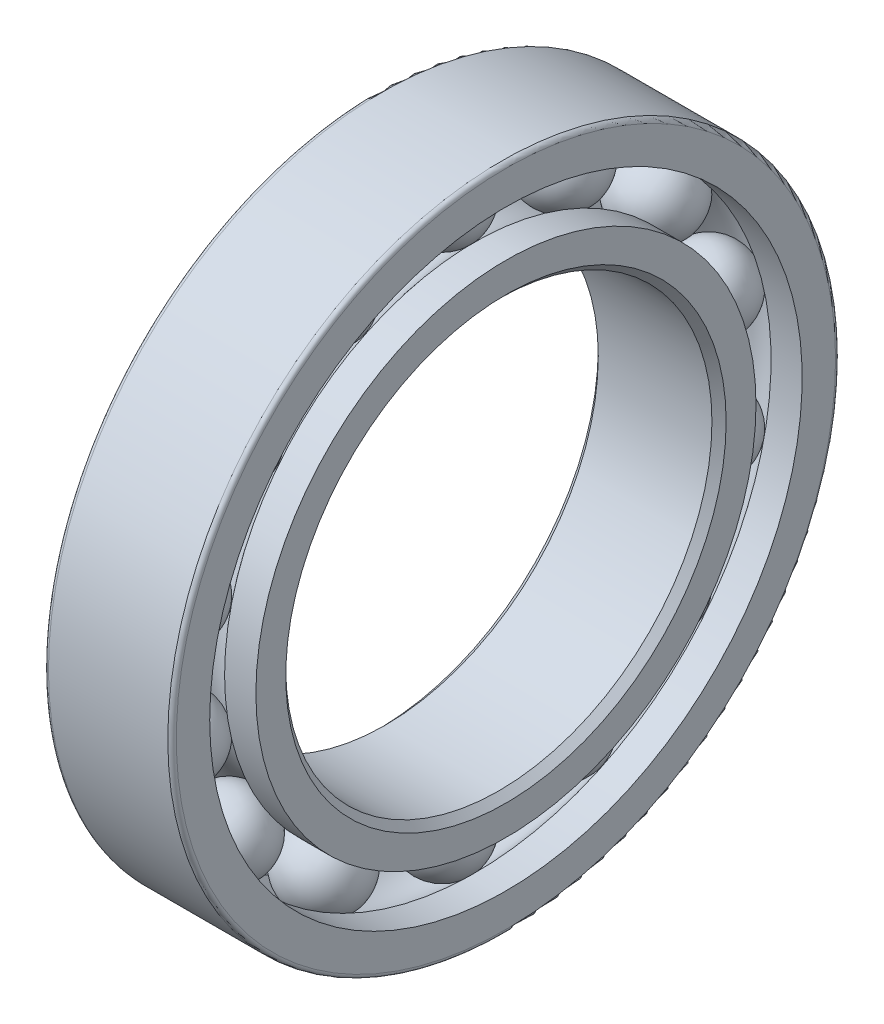
SolidWorks part; units mm, degrees
ref_plane "Front Plane" through (0, 0, 0) normal (0, 0, 1) x (1, 0, 0)
ref_plane "Top Plane" through (0, 0, 0) normal (0, 1, 0) x (1, 0, 0)
ref_plane "Right Plane" through (0, 0, 0) normal (1, 0, 0) x (0, 0, -1)
sketch "Sketch1" plane through (0, 0, 0) normal (0, 0, 1) x (1, 0, 0)
  line L0 (-39.0341, 0) -> (0, 0) construction
  line L1 (0, 0) -> (0, 22.175) construction
  line L3 (4.5, 23.5) -> (-4.5, 23.5)
  line L4 (4.5, 23.5) -> (4.5, 20.85)
  line L5 (4.5, 20.85) -> (-4.5, 20.85)
  line L6 (-4.5, 23.5) -> (-4.5, 20.85)
  line L7 (4.5, 23.5) -> (-4.5, 20.85) construction
  line L8 (4.5, 20.85) -> (-4.5, 23.5) construction
  line L9 (4.5, 17.6) -> (-4.5, 17.6)
  line L10 (4.5, 17.6) -> (4.5, 15)
  line L11 (4.5, 15) -> (-4.5, 15)
  line L12 (-4.5, 17.6) -> (-4.5, 15)
  line L13 (4.5, 17.6) -> (-4.5, 15) construction
  line L14 (4.5, 15) -> (-4.5, 17.6) construction
  circle A0 centre (0, 19.2353) radius 2.82
  point P9 (0, 16.3)
  dimension "D1" = 15
  dimension "D2" = 23.5
  dimension "D3" = 9
  dimension "D4" = 17.6
  dimension "D5" = 20.85
revolve "Revolve1" add sketch "Sketch1" angle 360 about L0 region at (0, 22.3383, 0) region at (0, 16.141, 0)
sketch "Sketch2" plane through (0, 0, 0) normal (0, 0, 1) x (1, 0, 0)
  line L0 (-2.8, 19.24) -> (2.8, 19.24)
  circle A0 centre (0, 19.24) radius 2.8
  point P4 (0, 0)
  dimension "D1" = 19.24
  dimension "D2" = 5.6
revolve "Revolve2" add sketch "Sketch2" angle 360 about L0 region at (0, 20.4284, 0)
ref_axis "Axis1" through (4.5, 0, 0) along (-1, 0, 0)
pattern_circular "CirPattern1" count 14 over 360 about axis through (4.5, 0, 0) along (-1, 0, 0) of bodies 103
fillet "Fillet1" radius 0.3 2 edges at (4.5, 0, 23.5) (-4.5, 0, 23.5)
chamfer "Chamfer1" distance 0.5 angle 45 2 edges at (4.5, 0, 15) (-4.5, 0, 15)
